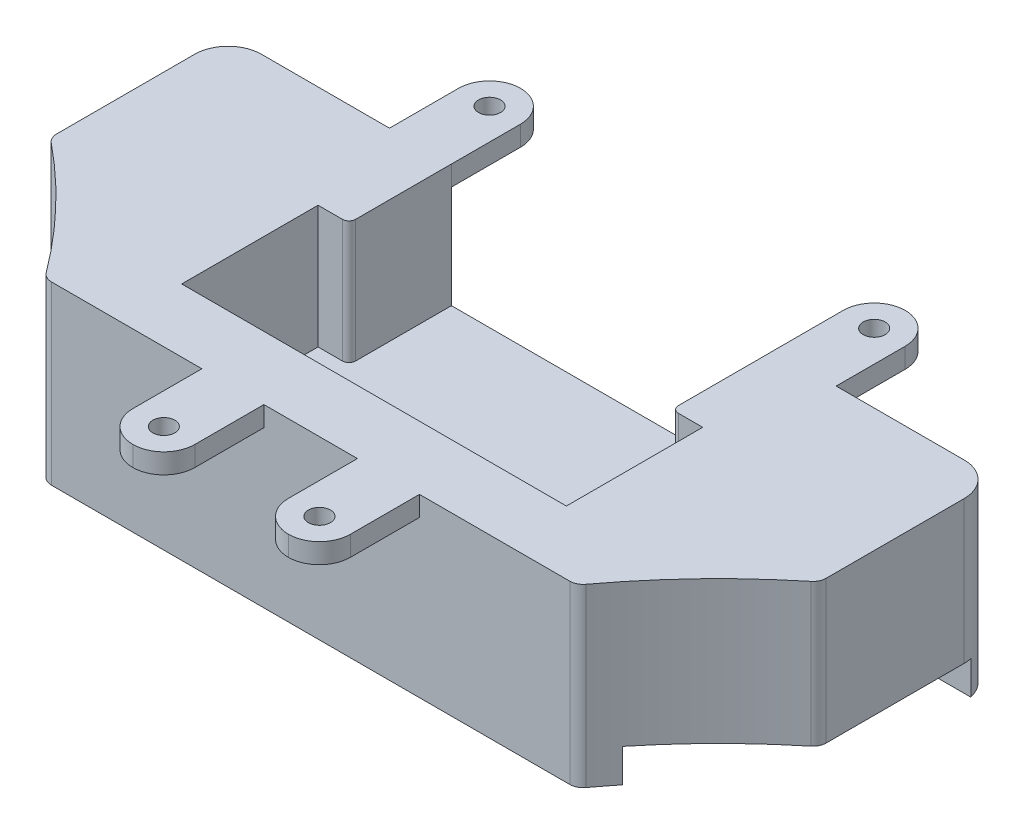
SolidWorks part; units mm, degrees
ref_plane "Alzado" through (0, 0, 0) normal (0, 0, 1) x (1, 0, 0)
ref_plane "Planta" through (0, 0, 0) normal (0, 1, 0) x (1, 0, 0)
ref_plane "Vista lateral" through (0, 0, 0) normal (1, 0, 0) x (0, 0, -1)
sketch "Croquis2" plane through (0, 0, 0) normal (0, 1, 0) x (1, 0, 0)
  line L0 (57.685, 41.3) -> (57.685, 4) construction
  line L1 (0, 0) -> (115.37, 0)
  line L2 (0, 0) -> (0, 45.3)
  line L3 (0, 45.3) -> (115.37, 45.3)
  line L4 (115.37, 0) -> (115.37, 45.3)
  line L5 (0.05, 41.3) -> (115.32, 41.3) construction
  line L6 (0.05, 41.3) -> (0.05, 4) construction
  line L7 (0.05, 4) -> (115.32, 4) construction
  line L8 (115.32, 41.3) -> (115.32, 4) construction
  line L9 (0, 22.65) -> (115.37, 22.65) construction
  circle A0 centre (57.685, 19.5) radius 3.25
  circle A1 centre (75.685, 19.5) radius 1.65
  circle A2 centre (39.685, 19.5) radius 1.65
  point P9 (57.685, 41.3)
  point P10 (57.685, 45.3)
  point P11 (57.685, 4)
  point P12 (57.685, 0)
  point P13 (0.05, 22.65)
  point P14 (0, 22.65)
  point P15 (115.32, 22.65)
  point P16 (115.37, 22.65)
  dimension "D6" = 6.5
  dimension "D8" = 3.3
  dimension "D1" = 45.3
  dimension "D2" = 115.37
  dimension "D3" = 37.3
  dimension "D4" = 115.27
  dimension "D5" = 21.8
  dimension "D7" = 18
extrude "Saliente-Extruir1" add sketch "Croquis2" along normal blind 21.4
sketch "Croquis6" plane through (0, 21.4, 0) normal (0, 1, 0) x (1, 0, 0)
  line L0 (115.37, 45.3) -> (0, 45.3) construction
  line L1 (33.495, 45.3) -> (81.875, 45.3)
  line L2 (33.495, 45.3) -> (33.495, 9.5)
  line L3 (33.495, 9.5) -> (81.875, 9.5)
  line L4 (81.875, 45.3) -> (81.875, 9.5)
  circle A0 centre (57.685, 19.5) radius 3.25 construction
  circle A1 centre (39.685, 19.5) radius 1.65 construction
  point P6 (57.685, 45.3)
  point P7 (57.685, 45.3)
  dimension "D1" = 10
  dimension "D2" = 6.19
extrude "Cortar-Extruir1" cut sketch "Croquis6" against normal blind 18.4
sketch "Croquis9" plane through (0, 21.4, 0) normal (0, 1, 0) x (1, 0, 0)
  line L0 (115.37, 22.65) -> (0, 22.65) construction
  line L1 (115.37, 0) -> (115.37, 45.3) construction
  line L2 (0, 45.3) -> (0, 0) construction
  line L3 (57.685, 0) -> (57.685, 45.3) construction
  line L4 (0, 0) -> (115.37, 0) construction
  line L5 (81.875, 45.3) -> (33.495, 45.3) construction
  line L6 (115.37, 45.3) -> (81.875, 45.3) construction
  line L7 (91.17, 45.3) -> (81.87, 45.3)
  line L8 (91.17, 45.3) -> (91.17, 60.3)
  line L9 (91.17, 60.3) -> (81.87, 60.3)
  line L10 (81.87, 45.3) -> (81.87, 60.3)
  line L11 (86.52, 60.3) -> (86.52, 45.3) construction
  line L12 (24.2, 60.3) -> (33.5, 60.3)
  line L13 (33.5, 45.3) -> (33.5, 60.3)
  line L14 (24.2, 45.3) -> (33.5, 45.3)
  line L15 (24.2, 45.3) -> (24.2, 60.3)
  line L16 (69.345, -15) -> (69.345, 0) construction
  line L17 (73.995, 0) -> (64.695, 0)
  line L18 (73.995, 0) -> (73.995, -15)
  line L19 (73.995, -15) -> (64.695, -15)
  line L20 (64.695, 0) -> (64.695, -15)
  line L21 (41.375, -15) -> (50.675, -15)
  line L22 (50.675, 0) -> (50.675, -15)
  line L23 (41.375, 0) -> (50.675, 0)
  line L24 (41.375, 0) -> (41.375, -15)
  circle A0 centre (86.52, 55.65) radius 1.65
  circle A1 centre (28.85, 55.65) radius 1.65
  circle A2 centre (69.345, -10.35) radius 1.65
  circle A3 centre (46.025, -10.35) radius 1.65
  point P18 (86.52, 60.3)
  point P33 (69.345, -15)
  dimension "D4" = 3.3
  dimension "D9" = 3.3
  dimension "D1" = 28.85
  dimension "D2" = 4.65
  dimension "D3" = 15
  dimension "D5" = 4.65
  dimension "D6" = 11.66
  dimension "D7" = 9.3
  dimension "D8" = 15
  dimension "D10" = 4.65
extrude "Saliente-Extruir4" add sketch "Croquis9" against normal blind 3
fillet "Redondeo8" radius 4.65 8 edges at (73.995, 19.9, 15) (64.695, 19.9, 15) (41.375, 19.9, 15) (50.675, 19.9, 15) (91.17, 19.9, -60.3) (81.87, 19.9, -60.3) (33.5, 19.9, -60.3) (24.2, 19.9, -60.3)
sketch "Croquis7" plane through (0, 0, 0) normal (0, -1, 0) x (1, 0, 0)
  line L0 (57.685, 0) -> (57.685, -45.3) construction
  line L1 (0, 0) -> (115.37, 0) construction
  line L2 (115.37, -45.3) -> (0, -45.3) construction
  line L3 (0, -22.65) -> (115.37, -22.65) construction
  line L4 (0, -45.3) -> (0, 0) construction
  line L5 (115.37, 0) -> (115.37, -45.3) construction
  line L6 (0, -41.4) -> (115.37, -41.4)
  line L7 (0.05, -41.3) -> (115.32, -41.3) construction
  line L8 (0.05, -41.3) -> (0.05, -4) construction
  line L9 (0.05, -4) -> (115.32, -4) construction
  line L10 (115.32, -41.3) -> (115.32, -4) construction
  line L11 (0, 0) -> (115.37, 0)
  line L12 (0, 0) -> (0, -3.9)
  line L13 (0, -3.9) -> (115.37, -3.9)
  line L14 (115.37, 0) -> (115.37, -3.9)
  line L15 (115.37, -45.3) -> (115.37, -41.4)
  line L16 (0, -45.3) -> (115.37, -45.3)
  line L17 (0, -45.3) -> (0, -41.4)
  point P16 (57.685, -41.3)
  point P17 (57.685, -4)
  point P18 (0.05, -22.65)
  point P19 (115.32, -22.65)
  dimension "D1" = 37.3
  dimension "D2" = 115.27
  dimension "D3" = 3.9
extrude "Saliente-Extruir3" add sketch "Croquis7" along normal blind 5
fillet "Redondeo2" radius 5 4 edges at (0, 8.2, 0) (0, 8.2, -45.3) (115.37, 8.2, -45.3) (115.37, 8.2, 0)
sketch "Croquis11" plane through (0, 21.4, 0) normal (0, 1, 0) x (1, 0, 0)
  line L0 (57.685, 0) -> (57.685, 45.3) construction
  line L1 (50.675, 0) -> (64.695, 0) construction
  line L2 (81.875, 45.3) -> (33.495, 45.3) construction
  line L3 (115.37, 18.6477) -> (115.37, 5)
  line L4 (110.37, 0) -> (97.5501, 0)
  line L5 (73.995, 0) -> (110.37, 0) construction
  line L7 (0, 18.6477) -> (0, 5)
  line L8 (5, 0) -> (17.8199, 0)
  arc A0 (115.37, 5) -> (110.37, 0) centre (110.37, 5) cw
  arc A1 (115.37, 18.6477) -> (97.5501, 0) centre (175.2659, -56.4273) ccw
  arc A2 (0, 5) -> (5, 0) centre (5, 5) ccw
  arc A3 (0, 18.6477) -> (17.8199, 0) centre (-59.8959, -56.4273) cw
  dimension "D1" = 96.0405
  dimension "D2" = 59.8959
  dimension "D3" = 56.4273
extrude "Cortar-Extruir2" cut sketch "Croquis11" against normal through all
fillet "Redondeo9" radius 2 4 edges at (17.8199, 8.2, 0) (0, 10.7, -18.6477) (97.5501, 8.2, 0) (115.37, 10.7, -18.6477)
sketch "Croquis12" plane through (0, 21.4, 0) normal (0, 1, 0) x (1, 0, 0)
  line L0 (57.685, 16.25) -> (57.685, 9.5) construction
  line L1 (33.495, 9.5) -> (81.875, 9.5) construction
  line L2 (57.685, 22.75) -> (57.685, 29.94) construction
  line L3 (28.85, 60.3) -> (28.85, 9.5) construction
  line L4 (28.85, 29.94) -> (86.52, 29.94)
  line L5 (28.85, 29.94) -> (28.85, 9.5)
  line L6 (28.85, 9.5) -> (86.52, 9.5)
  line L7 (86.52, 29.94) -> (86.52, 9.5)
  line L9 (86.52, 60.3) -> (86.52, 9.5) construction
  circle A0 centre (57.685, 19.5) radius 3.25 construction
  point P13 (57.685, 29.94)
  point P14 (57.685, 9.5)
  dimension "D1" = 7.19
  dimension "D2" = 90
extrude "Cortar-Extruir3" cut sketch "Croquis12" against normal up to surface (18.4 mm away) up to face at (57.685, 3, -16.25)
fillet "Redondeo10" radius 1 2 edges at (81.875, 12.2, -29.94) (33.495, 12.2, -29.94)
